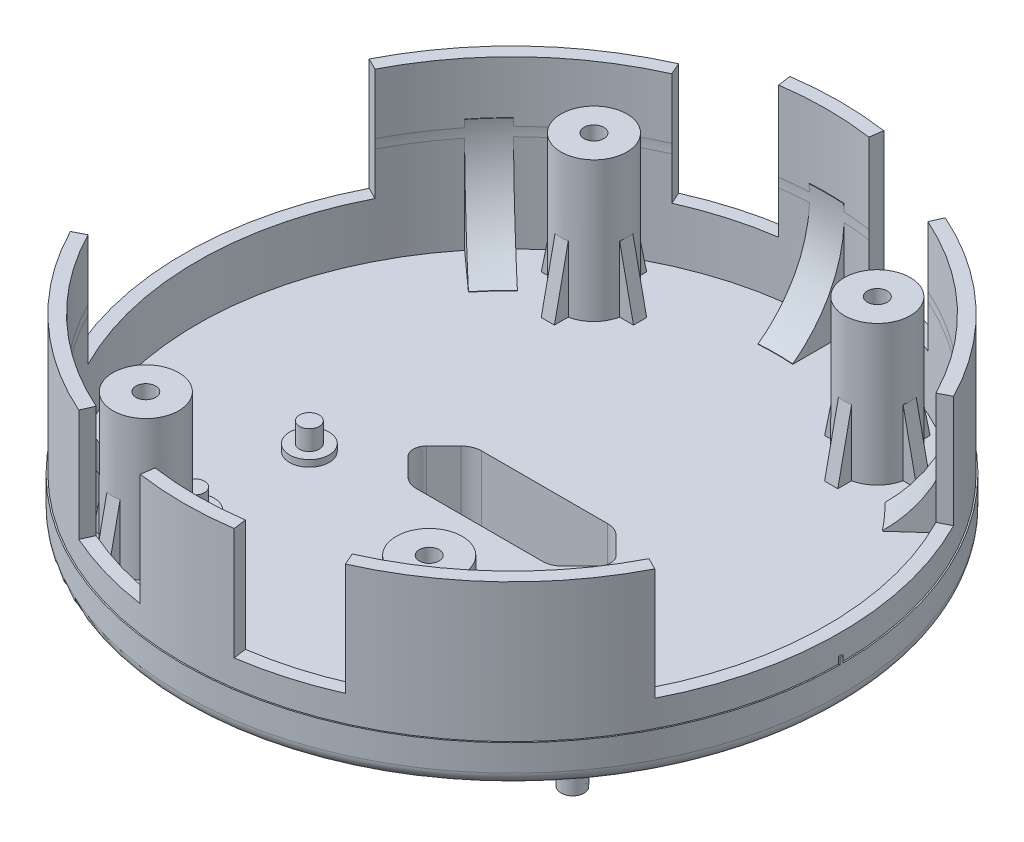
SolidWorks part; units mm, degrees
ref_plane "Front Plane" through (0, 0, 0) normal (0, 0, 1) x (1, 0, 0)
ref_plane "Top Plane" through (0, 0, 0) normal (0, 1, 0) x (1, 0, 0)
ref_plane "Right Plane" through (0, 0, 0) normal (1, 0, 0) x (0, 0, -1)
sketch "Эскиз1" plane through (0, 0, 0) normal (0, 1, 0) x (1, 0, 0)
  circle A0 centre (0, 0) radius 50
  dimension "D1" = 100
extrude "Бобышка-Вытянуть1" add sketch "Эскиз1" along normal blind 6
shell "Оболочка1" thickness 2 removed face at (0, 6, 50)
sketch "Эскиз3" plane through (0, 2, 0) normal (0, 1, 0) x (1, 0, 0)
  circle A0 centre (0, 0) radius 48 construction
  circle A1 centre (0, 0) radius 48
extrude "Бобышка-Вытянуть2" add sketch "Эскиз3" along normal blind 2
fillet "Скругление1" radius 2 1 edges at (0, 0, 50)
sketch "Эскиз4" plane through (0, 4, 0) normal (0, 1, 0) x (1, 0, 0)
  circle A2 centre (0, 0) radius 47.8
  circle A3 centre (0, 0) radius 49.8
  dimension "D1" = 99.6
  dimension "D2" = 95.6
extrude "Бобышка-Вытянуть3" add sketch "Эскиз4" along normal blind 23
sketch "Эскиз8" plane through (0, 0, 0) normal (0, -1, 0) x (1, 0, 0)
  line L0 (-17.136, 1.486) -> (-13.1647, 5.4574)
  line L1 (-9.5574, 6.9516) -> (9.5574, 6.9516)
  line L2 (13.1647, 5.4574) -> (17.136, 1.486)
  line L3 (17.136, -1.486) -> (13.1647, -5.4574)
  line L4 (9.5574, -6.9516) -> (-9.5574, -6.9516)
  line L5 (-13.1647, -5.4574) -> (-17.136, -1.486)
  line L6 (0, 6.9516) -> (0, -6.9516) construction
  line L7 (-15.65, 0) -> (15.65, 0) construction
  arc A0 (-9.5574, 6.9516) -> (-13.1647, 5.4574) centre (-9.5574, 1.85) ccw
  arc A1 (13.1647, 5.4574) -> (9.5574, 6.9516) centre (9.5574, 1.85) ccw
  arc A2 (17.136, -1.486) -> (17.136, 1.486) centre (15.65, 0) ccw
  arc A3 (9.5574, -6.9516) -> (13.1647, -5.4574) centre (9.5574, -1.85) ccw
  arc A4 (-13.1647, -5.4574) -> (-9.5574, -6.9516) centre (-9.5574, -1.85) ccw
  arc A5 (-17.136, 1.486) -> (-17.136, -1.486) centre (-15.65, 0) ccw
  circle A6 centre (0, 0) radius 48 construction
  dimension "D1" = 5.1016
  dimension "D2" = 2.1016
  dimension "D3" = 9.5574
  dimension "D4" = 15.65
  dimension "D5" = 9.5574
  dimension "D6" = 1.486
extrude "Бобышка-Вытянуть4" add sketch "Эскиз8" along normal blind 20
sketch "Эскиз9" plane through (0, 4, 0) normal (0, 1, 0) x (1, 0, 0)
  line L0 (-14.3803, 1.4134) -> (-11.7505, 4.0431)
  line L1 (-11.7505, -4.0431) -> (-14.3803, -1.4134)
  line L2 (9.5574, -4.9516) -> (-9.5574, -4.9516)
  line L3 (14.3803, -1.4134) -> (11.7505, -4.0431)
  line L4 (11.7505, 4.0431) -> (14.3803, 1.4134)
  line L5 (-9.5574, 4.9516) -> (9.5574, 4.9516)
  line L6 (0, 4.9516) -> (0, -4.9516) construction
  line L7 (-10.9611, 0) -> (10.9611, 0) construction
  arc A0 (-11.7505, -4.0431) -> (-9.5574, -4.9516) centre (-9.5574, -1.85) ccw
  arc A1 (9.5574, -4.9516) -> (11.7505, -4.0431) centre (9.5574, -1.85) ccw
  arc A2 (11.7505, 4.0431) -> (9.5574, 4.9516) centre (9.5574, 1.85) ccw
  arc A3 (-9.5574, 4.9516) -> (-11.7505, 4.0431) centre (-9.5574, 1.85) ccw
  circle A4 centre (0, 0) radius 49.8 construction
  ellipse E0 centre (-12.9635, 0) end of major axis (-10.9611, 0) minor radius 2 (-14.3803, 1.4134) -> (-14.3803, -1.4134) ccw
  ellipse E1 centre (12.9635, 0) end of major axis (10.9611, 0) minor radius 2 (14.3803, -1.4134) -> (14.3803, 1.4134) ccw
  dimension "D1" = 3.1016
  dimension "D2" = 9.5574
  dimension "D3" = 10.9611
  dimension "D4" = 12.9635
  dimension "D5" = 14.3803
  dimension "D6" = 9.5574
  dimension "D7" = 10.9611
  dimension "D8" = 1.85
  dimension "D9" = 1.85
extrude "Вырез-Вытянуть3" cut sketch "Эскиз9" against normal blind 22.5
sketch "Эскиз10" plane through (0, -18.5, 0) normal (0, 1, 0) x (1, 0, 0)
  line L0 (0, 0) -> (9.4, 0) construction
  line L1 (0, 0) -> (-9.4, 0) construction
  circle A0 centre (-9.4, 0) radius 3.5
  circle A1 centre (9.4, 0) radius 3.5
  dimension "D1" = 7
  dimension "D2" = 4.9803
extrude "Бобышка-Вытянуть5" add sketch "Эскиз10" along normal blind 6
sketch "Эскиз15" plane through (0, 4, 0) normal (0, 1, 0) x (1, 0, 0)
  circle A0 centre (0, 0) radius 50
  circle A1 centre (0, 0) radius 48
  dimension "D1" = 96
  dimension "D2" = 100
extrude "Бобышка-Вытянуть9" add sketch "Эскиз15" along normal blind 2
sketch "Эскиз16" plane through (0, 4, 0) normal (0, 1, 0) x (1, 0, 0)
  line L0 (-37.2524, 30.063) -> (-31.4039, 24.7971)
  line L1 (0, 47.8) -> (2.6705, 47.8) construction
  line L2 (0, 47.8) -> (-2.5855, 47.8) construction
  line L14 (-2.5855, 47.8) -> (-2.5855, 39.9302)
  line L15 (-33.7354, 33.969) -> (-27.8829, 28.6993)
  line L24 (0, 47.8) -> (2.6705, 47.8) construction
  line L25 (2.6705, 47.8) -> (2.6705, 39.9246)
  line L33 (0, 47.8) -> (-2.5855, 47.8) construction
  line L34 (0, 0) -> (0, 14.9931) construction
  line L37 (0, 0) -> (22.7819, 0) construction
  line L38 (0, -47.8) -> (-2.5855, -47.8) construction
  line L41 (33.7354, 33.969) -> (27.8829, 28.6993)
  line L42 (37.2524, 30.063) -> (31.4039, 24.7971)
  line L43 (0, -47.8) -> (2.6705, -47.8) construction
  line L44 (0, -47.8) -> (-2.5855, -47.8) construction
  line L45 (0, -47.8) -> (2.6705, -47.8) construction
  line L46 (37.2524, -30.063) -> (31.4039, -24.7971)
  line L47 (33.7354, -33.969) -> (27.8829, -28.6993)
  line L48 (2.6705, -47.8) -> (2.6705, -39.9246)
  line L49 (-33.7354, -33.969) -> (-27.8829, -28.6993)
  line L50 (-2.5855, -47.8) -> (-2.5855, -39.9302)
  line L51 (-37.2524, -30.063) -> (-31.4039, -24.7971)
  circle A18 centre (0, 0) radius 47.8 construction
  arc A19 (-33.68, 33.919) -> (-37.2004, 30.0162) centre (0, 0) ccw
  arc A20 (-27.8829, 28.6993) -> (-31.4039, 24.7971) centre (0, 0) ccw
  arc A21 (2.6705, 47.7253) -> (-2.5855, 47.73) centre (0, 0) ccw
  arc A22 (2.6705, 39.9246) -> (-2.5855, 39.9302) centre (0, 0) ccw
  arc A23 (33.68, -33.919) -> (37.2004, -30.0162) centre (0, 0) ccw
  arc A24 (27.8829, -28.6993) -> (31.4039, -24.7971) centre (0, 0) ccw
  arc A25 (2.6705, -39.9246) -> (-2.5855, -39.9302) centre (0, 0) cw
  arc A26 (2.6705, -47.7253) -> (-2.5855, -47.73) centre (0, 0) cw
  arc A27 (-27.8829, -28.6993) -> (-31.4039, -24.7971) centre (0, 0) cw
  arc A28 (-33.68, -33.919) -> (-37.2004, -30.0162) centre (0, 0) cw
  arc A29 (27.8829, 28.6993) -> (31.4039, 24.7971) centre (0, 0) cw
  arc A30 (33.68, 33.919) -> (37.2004, 30.0162) centre (0, 0) cw
extrude "Бобышка-Вытянуть10" add sketch "Эскиз16" along normal blind 15
sketch "Эскиз27" plane through (0, 6, 0) normal (0, 1, 0) x (1, 0, 0)
  line L0 (0, 0) -> (-65.748, 0) construction
  line L1 (0, 0) -> (0, 13.4164) construction
  line L14 (49.9994, -0.2541) -> (49.7994, -0.2541)
  line L17 (49.9994, 0.2541) -> (49.7994, 0.2541)
  line L18 (-49.9994, 0.2541) -> (-49.7994, 0.2541)
  line L19 (-49.9994, -0.2541) -> (-49.7994, -0.2541)
  arc A0 (-49.9994, 0.2541) -> (-49.9994, -0.2541) centre (0, 0) ccw
  arc A2 (-49.7994, 0.2541) -> (-49.7994, -0.2541) centre (0, 0) ccw
  arc A13 (49.7994, 0.2541) -> (49.7994, -0.2541) centre (0, 0) cw
  arc A14 (49.9994, 0.2541) -> (49.9994, -0.2541) centre (0, 0) cw
extrude "Бобышка-Вытянуть14" add sketch "Эскиз27" along normal blind 1
sketch "Эскиз28" plane through (0, 4, 0) normal (0, 1, 0) x (1, 0, 0)
  line L0 (-37.2004, 30.0162) -> (-31.4039, 24.7971) construction
  line L2 (-37.2004, 30.0162) -> (-31.4039, 24.7971)
  line L5 (-33.68, 33.919) -> (-27.8829, 28.6993) construction
  line L7 (-33.68, 33.919) -> (-27.8829, 28.6993)
  line L9 (-2.5855, 47.73) -> (-2.5855, 39.9302) construction
  line L11 (-2.5855, 47.73) -> (-2.5855, 39.9302)
  line L14 (2.6705, 47.7253) -> (2.6705, 39.9246) construction
  line L16 (2.6705, 47.7253) -> (2.6705, 39.9246)
  line L19 (33.68, 33.919) -> (27.8829, 28.6993) construction
  line L21 (33.68, 33.919) -> (27.8829, 28.6993)
  line L28 (37.2004, 30.0162) -> (31.4039, 24.7971) construction
  line L30 (37.2004, 30.0162) -> (31.4039, 24.7971)
  line L38 (37.2004, -30.0162) -> (31.4039, -24.7971) construction
  line L39 (37.2004, -30.0162) -> (31.4039, -24.7971)
  line L40 (33.68, -33.919) -> (27.8829, -28.6993) construction
  line L41 (33.68, -33.919) -> (27.8829, -28.6993)
  line L42 (2.6705, -47.7253) -> (2.6705, -39.9246) construction
  line L43 (2.6705, -47.7253) -> (2.6705, -39.9246)
  line L44 (-2.5855, -47.73) -> (-2.5855, -39.9302) construction
  line L45 (-2.5855, -47.73) -> (-2.5855, -39.9302)
  line L46 (-33.68, -33.919) -> (-27.8829, -28.6993) construction
  line L47 (-33.68, -33.919) -> (-27.8829, -28.6993)
  line L48 (-37.2004, -30.0162) -> (-31.4039, -24.7971) construction
  line L49 (-37.2004, -30.0162) -> (-31.4039, -24.7971)
  arc A0 (-37.2004, 30.0162) -> (-37.2004, -30.0162) centre (0, 0) ccw construction
  arc A2 (-37.2004, 30.0162) -> (-37.2004, -30.0162) centre (0, 0) ccw
  arc A4 (-27.8829, 28.6993) -> (-31.4039, 24.7971) centre (0, 0) ccw construction
  arc A6 (-27.8829, 28.6993) -> (-31.4039, 24.7971) centre (0, 0) ccw
  arc A8 (-2.5855, 47.73) -> (-33.68, 33.919) centre (0, 0) ccw construction
  arc A10 (-2.5855, 47.73) -> (-33.68, 33.919) centre (0, 0) ccw
  arc A14 (2.6705, 39.9246) -> (-2.5855, 39.9302) centre (0, 0) ccw construction
  arc A16 (2.6705, 39.9246) -> (-2.5855, 39.9302) centre (0, 0) ccw
  arc A17 (33.68, 33.919) -> (2.6705, 47.7253) centre (0, 0) ccw construction
  arc A18 (33.68, 33.919) -> (2.6705, 47.7253) centre (0, 0) ccw
  arc A19 (31.4039, 24.7971) -> (27.8829, 28.6993) centre (0, 0) ccw construction
  arc A20 (31.4039, 24.7971) -> (27.8829, 28.6993) centre (0, 0) ccw
  arc A21 (37.2004, -30.0162) -> (37.2004, 30.0162) centre (0, 0) ccw construction
  arc A22 (37.2004, -30.0162) -> (37.2004, 30.0162) centre (0, 0) ccw
  arc A23 (27.8829, -28.6993) -> (31.4039, -24.7971) centre (0, 0) ccw construction
  arc A24 (27.8829, -28.6993) -> (31.4039, -24.7971) centre (0, 0) ccw
  arc A25 (2.6705, -47.7253) -> (33.68, -33.919) centre (0, 0) ccw construction
  arc A26 (2.6705, -47.7253) -> (33.68, -33.919) centre (0, 0) ccw
  arc A27 (-2.5855, -39.9302) -> (2.6705, -39.9246) centre (0, 0) ccw construction
  arc A28 (-2.5855, -39.9302) -> (2.6705, -39.9246) centre (0, 0) ccw
  arc A29 (-33.68, -33.919) -> (-2.5855, -47.73) centre (0, 0) ccw construction
  arc A30 (-33.68, -33.919) -> (-2.5855, -47.73) centre (0, 0) ccw
  arc A31 (-31.4039, -24.7971) -> (-27.8829, -28.6993) centre (0, 0) ccw construction
  arc A32 (-31.4039, -24.7971) -> (-27.8829, -28.6993) centre (0, 0) ccw
ref_plane "Плоскость2" through (0, 0, 0) normal (0, 0, 1) x (1, 0, 0)
sketch "Эскиз29" plane through (0, 0, 0) normal (0, 0, 1) x (1, 0, 0)
  line L1 (7.5729, -23.4603) -> (7.4167, -30.4586)
  line L10 (9.4089, -19.6) -> (9.3224, -23.4991)
  line L11 (7.4589, -19.6) -> (9.4089, -19.6)
  line L12 (7.4589, -19.6) -> (7.3729, -23.4559)
  line L13 (0, -20) -> (0, -16.8479) construction
  line L14 (9.5574, -20) -> (-9.5574, -20) construction
  line L15 (7.3729, -23.4559) -> (7.5729, -23.4603)
  line L16 (7.4167, -30.4586) -> (9.1672, -30.4972)
  line L17 (9.3224, -23.4991) -> (9.2359, -27.3983)
  line L18 (9.2359, -27.3983) -> (9.1672, -30.4972)
revolve "Повернуть4" add sketch "Эскиз29" angle 360 about L10
sketch "Эскиз30" plane through (0, 0, 0) normal (0, 0, 1) x (1, 0, 0)
  line L4 (0, -20) -> (0, -16.0591) construction
  line L5 (9.5574, -20) -> (-9.5574, -20) construction
  line L10 (-9.4076, -19.6) -> (-9.3216, -23.4559)
  line L11 (-9.4076, -19.6) -> (-11.3576, -19.6)
  line L12 (-11.3576, -19.6) -> (-11.2711, -23.4991)
  line L14 (-11.0712, -23.4949) -> (-10.9159, -30.4932)
  line L15 (-11.3576, -19.6) -> (-11.3576, -20) construction
  line L16 (-11.2711, -23.4991) -> (-11.0712, -23.4949)
  line L17 (-10.9159, -30.4932) -> (-9.1663, -30.4566)
  line L18 (-9.3216, -23.4559) -> (-9.2351, -27.3551)
  line L19 (-9.2351, -27.3551) -> (-9.1663, -30.4566)
revolve "Повернуть5" add sketch "Эскиз30" angle 360 about L10
sketch "Эскиз32" plane through (0, 0, 0) normal (0, 0, 1) x (1, 0, 0)
  line L1 (7.9675, -30.4708) -> (8.2159, -19.2736)
  line L2 (8.2159, -19.2736) -> (8.3158, -19.2758)
  line L3 (9.1672, -30.4972) -> (7.9675, -30.4708)
  line L4 (7.4167, -30.4586) -> (10.9176, -30.5362) construction
  line L6 (8.4933, -11.2777) -> (8.3158, -19.2758)
  line L9 (8.4933, -11.2777) -> (9.593, -11.3019)
  line L10 (9.593, -11.3019) -> (9.1672, -30.4972)
revolve "Вырез-Повернуть2" cut sketch "Эскиз32" angle 360 about L10
sketch "Эскиз33" plane through (0, 0, 0) normal (0, 0, 1) x (1, 0, 0)
  line L8 (-9.5913, -11.2615) -> (-9.1654, -30.4568)
  line L11 (-8.4915, -11.2373) -> (-9.5913, -11.2615)
  line L12 (-8.4915, -11.2373) -> (-8.3141, -19.2353)
  line L13 (-9.1654, -30.4568) -> (-7.9657, -30.4304)
  line L14 (-8.2141, -19.2331) -> (-8.3141, -19.2353)
  line L15 (-7.9657, -30.4304) -> (-8.2141, -19.2331)
revolve "Вырез-Повернуть3" cut sketch "Эскиз33" angle 360 about L8
chamfer "Фаска1" distance 0.2 angle 45 2 edges at (8.3158, -19.2758, 0) (-10.5136, -19.2841, 0) first distance on face at (10.6667, -12.5, 0) first distance on face at (-10.6641, -12.5, 0)
extrude "Вырез-Вытянуть11" cut sketch "Эскиз28" against normal blind 2.2538
sketch "Эскиз34" plane through (0, 27, 0) normal (0, 1, 0) x (1, 0, 0)
  line L1 (-6.8438, 47.3075) -> (-7.1302, 49.2869)
  line L2 (6.8438, 47.3075) -> (7.1302, 49.2869)
  line L7 (6.8438, -47.3075) -> (7.1302, -49.2869)
  line L8 (-6.8438, -47.3075) -> (-7.1302, -49.2869)
  line L20 (-0.0643, -46.931) -> (-0.0643, -36.9011) construction
  line L23 (-19.4216, -43.6765) -> (-20.2342, -45.504)
  line L24 (19.4216, -43.6765) -> (20.2342, -45.504)
  line L25 (19.4216, 43.6765) -> (20.2342, 45.504)
  line L26 (-19.4216, 43.6765) -> (-20.2342, 45.504)
  line L27 (-42.5581, 21.7634) -> (-44.3388, 22.674)
  line L28 (-42.5581, -21.7634) -> (-44.3388, -22.674)
  line L29 (42.5581, -21.7634) -> (44.3388, -22.674)
  line L30 (42.5581, 21.7634) -> (44.3388, 22.674)
  circle A44 centre (0, 0) radius 47.8 construction
  arc A45 (-6.8438, 47.3075) -> (-19.4216, 43.6765) centre (0, 0) ccw
  circle A46 centre (0, 0) radius 49.8 construction
  arc A47 (-7.1302, 49.2869) -> (-20.2342, 45.504) centre (0, 0) ccw
  arc A48 (-44.3388, 22.674) -> (-44.3388, -22.674) centre (0, 0) ccw
  arc A49 (-42.5581, 21.7634) -> (-42.5581, -21.7634) centre (0, 0) ccw
  arc A50 (20.2342, 45.504) -> (7.1302, 49.2869) centre (0, 0) ccw
  arc A51 (19.4216, 43.6765) -> (6.8438, 47.3075) centre (0, 0) ccw
  arc A52 (42.5581, -21.7634) -> (42.5581, 21.7634) centre (0, 0) ccw
  arc A53 (44.3388, -22.674) -> (44.3388, 22.674) centre (0, 0) ccw
  arc A54 (6.8438, -47.3075) -> (19.4216, -43.6765) centre (0, 0) ccw
  arc A55 (7.1302, -49.2869) -> (20.2342, -45.504) centre (0, 0) ccw
  arc A56 (-19.4216, -43.6765) -> (-6.8438, -47.3075) centre (0, 0) ccw
  arc A57 (-20.2342, -45.504) -> (-7.1302, -49.2869) centre (0, 0) ccw
extrude "Вырез-Вытянуть12" cut sketch "Эскиз34" against normal blind 17
sketch "Эскиз36" plane through (0, 1.7462, 0) normal (0, 1, 0) x (1, 0, 0)
  circle A0 centre (-22.6, -8.1516) radius 1.5
  circle A1 centre (22.6, -25.5516) radius 1.5
  circle A2 centre (22.6, -8.1516) radius 1.5
  circle A3 centre (-22.6, -25.5516) radius 1.5
extrude "Бобышка-Вытянуть15" add sketch "Эскиз36" along normal blind 4
sketch "Эскиз44" plane through (0, 1.7462, 0) normal (0, 1, 0) x (1, 0, 0)
  circle A0 centre (-22.6, -8.1516) radius 3
  circle A1 centre (22.6, -8.1516) radius 3
  circle A2 centre (-22.6, -25.5516) radius 3
  circle A3 centre (22.6, -25.5516) radius 3
extrude "Бобышка-Вытянуть17" add sketch "Эскиз44" along normal blind 1
sketch "Эскиз45" plane through (0, 0, 0) normal (1, 0, 0) x (0, 0, -1)
  line L0 (-47.7253, 19) -> (-39.9246, 19) construction
  line L1 (-47.7253, 19) -> (-39.9246, 19)
  line L2 (-39.9246, 19) -> (-39.9246, 1.7462) construction
  line L3 (-39.9246, 19) -> (-39.9246, 1.7462)
  line L4 (0, 0) -> (0, 15.2612) construction
  arc A0 (-47.7253, 19) -> (-39.9246, 1.7462) centre (-28.767, 17.1811) ccw
revolve "Вырез-Повернуть4" cut sketch "Эскиз45" angle 360 about L4
sketch "Эскиз47" plane through (0, 1.7462, 0) normal (0, 1, 0) x (1, 0, 0)
  line L0 (-0.0643, -46.931) -> (-0.0643, -36.9011) construction
  line L1 (0, 0) -> (7.0344, 0) construction
  line L2 (0, 0) -> (0, -4.9516) construction
  circle A0 centre (21.4357, 34) radius 5
  circle A1 centre (-21.5643, 34) radius 5
  circle A2 centre (-21.5643, -34) radius 5
  circle A3 centre (21.4357, -34) radius 5
  point P13 (-21.5643, 34)
  point P14 (0, 0)
extrude "Бобышка-Вытянуть18" add sketch "Эскиз47" along normal blind 21.25
sketch "Эскиз48" plane through (0, 22.9962, 0) normal (0, 1, 0) x (1, 0, 0)
  circle A0 centre (-21.5643, 34) radius 1.5
  circle A1 centre (21.4357, 34) radius 1.5
  circle A2 centre (21.4357, -34) radius 1.5
  circle A3 centre (-21.5643, -34) radius 1.5
  point P8 (-21.5643, 34)
  point P9 (21.4357, 34)
  point P10 (21.4357, -34)
  point P11 (-21.5643, -34)
  point P12 (21.4357, 34)
  point P13 (21.4357, 34)
extrude "Вырез-Вытянуть20" cut sketch "Эскиз48" against normal up to surface (22.9962 mm away) up to face at (0, 0, 48)
sketch "Эскиз50" plane through (0, 0, 0) normal (0, -1, 0) x (1, 0, 0)
  circle A0 centre (-21.5643, 34) radius 3.1
  circle A1 centre (21.4357, 34) radius 3.1
  circle A2 centre (21.4357, -34) radius 3.1
  circle A3 centre (-21.5643, -34) radius 3.1
  point P8 (21.4357, 34)
extrude "Вырез-Вытянуть21" cut sketch "Эскиз50" against normal blind 19
sketch "Эскиз51" plane through (0, 0, 0) normal (0, -1, 0) x (1, 0, 0)
  line L0 (0, 0) -> (0, 20) construction
  line L1 (-10, 35) -> (10, 35)
  line L2 (-10, 35) -> (-10, 20)
  line L3 (-10, 20) -> (10, 20)
  line L4 (10, 35) -> (10, 20)
  line L5 (-10, 35) -> (10, 20) construction
  line L6 (-10, 20) -> (10, 35) construction
  point P0 (0, 27.5)
  dimension "D1" = 20
  dimension "D2" = 15
extrude "Вырез-Вытянуть22" cut sketch "Эскиз51" against normal blind 0.1
sketch "Эскиз58" plane through (0, 1.7462, 0) normal (0, 1, 0) x (1, 0, 0)
  line L0 (26.4357, 34) -> (26.4357, 33) construction
  line L1 (26.4357, 35) -> (28.4357, 35)
  line L2 (20.4357, 39) -> (20.4357, 41)
  line L3 (22.4357, 29) -> (22.4357, 27)
  line L4 (-26.5643, 34) -> (-26.5643, 35) construction
  line L5 (-26.5643, 33) -> (-28.5643, 33)
  line L6 (-28.5643, 33) -> (-28.5643, 35)
  line L7 (-28.5643, 35) -> (-26.4633, 35)
  line L8 (-26.5643, 33) -> (-26.4633, 33)
  line L9 (-22.5643, 39) -> (-22.5643, 41)
  line L10 (-22.5643, 41) -> (-20.5643, 41)
  line L11 (-20.5643, 41) -> (-20.5643, 38.899)
  line L12 (-22.5643, 39) -> (-22.5643, 38.899)
  line L13 (-21.5643, 39) -> (-20.5643, 39) construction
  line L14 (-16.5643, 35) -> (-14.5643, 35)
  line L15 (-14.5643, 35) -> (-14.5643, 33)
  line L16 (-14.5643, 33) -> (-16.6653, 33)
  line L17 (-16.5643, 35) -> (-16.6653, 35)
  line L18 (-16.5643, 34) -> (-16.5643, 33) construction
  line L19 (-20.5643, 29) -> (-20.5643, 27)
  line L20 (-20.5643, 27) -> (-22.5643, 27)
  line L21 (-22.5643, 27) -> (-22.5643, 29.101)
  line L22 (-20.5643, 29) -> (-20.5643, 29.101)
  line L23 (-21.5643, 29) -> (-22.5643, 29) construction
  line L24 (20.4357, 27) -> (20.4357, 29.101)
  line L25 (22.4357, 41) -> (22.4357, 38.899)
  line L26 (21.4357, 29) -> (20.4357, 29) construction
  line L27 (26.4357, 35) -> (26.3347, 35)
  line L28 (16.4357, 34) -> (16.4357, 35) construction
  line L29 (14.4357, 33) -> (14.4357, 35)
  line L30 (20.4357, 39) -> (20.4357, 38.899)
  line L31 (22.4357, 27) -> (20.4357, 27)
  line L32 (28.4357, 35) -> (28.4357, 33)
  line L33 (14.4357, 35) -> (16.5367, 35)
  line L34 (28.4357, 33) -> (26.3347, 33)
  line L35 (22.4357, 29) -> (22.4357, 29.101)
  line L36 (21.4357, 39) -> (22.4357, 39) construction
  line L37 (16.4357, 33) -> (14.4357, 33)
  line L38 (20.4357, 41) -> (22.4357, 41)
  line L39 (16.4357, 33) -> (16.5367, 33)
  line L41 (14.4357, -33) -> (16.5367, -33)
  line L42 (-26.5643, -34) -> (-26.5643, -33) construction
  line L43 (-14.5643, -33) -> (-14.5643, -35)
  line L44 (-20.5643, -39) -> (-20.5643, -41)
  line L45 (16.4357, -35) -> (16.5367, -35)
  line L47 (28.4357, -33) -> (28.4357, -35)
  line L48 (22.4357, -39) -> (22.4357, -41)
  line L49 (-20.5643, -39) -> (-20.5643, -38.899)
  line L50 (16.4357, -34) -> (16.4357, -33) construction
  line L51 (-26.5643, -35) -> (-28.5643, -35)
  line L52 (20.4357, -41) -> (20.4357, -38.899)
  line L54 (26.4357, -33) -> (28.4357, -33)
  line L55 (-28.5643, -33) -> (-26.4633, -33)
  line L57 (-16.5643, -33) -> (-16.6653, -33)
  line L58 (-16.5643, -34) -> (-16.5643, -35) construction
  line L59 (-28.5643, -35) -> (-28.5643, -33)
  line L61 (26.4357, -33) -> (26.3347, -33)
  line L62 (16.4357, -35) -> (14.4357, -35)
  line L64 (28.4357, -35) -> (26.3347, -35)
  line L66 (22.4357, -41) -> (20.4357, -41)
  line L67 (-22.5643, -41) -> (-22.5643, -38.899)
  line L68 (-21.5643, -39) -> (-22.5643, -39) construction
  line L70 (26.4357, -34) -> (26.4357, -35) construction
  line L71 (-14.5643, -35) -> (-16.6653, -35)
  line L72 (14.4357, -35) -> (14.4357, -33)
  line L73 (22.4357, -39) -> (22.4357, -38.899)
  line L75 (-16.5643, -33) -> (-14.5643, -33)
  line L76 (-26.5643, -35) -> (-26.4633, -35)
  line L78 (-20.5643, -41) -> (-22.5643, -41)
  line L79 (21.4357, -39) -> (20.4357, -39) construction
  circle A3 centre (-21.5643, 34) radius 5 construction
  arc A7 (-26.4633, 35) -> (-26.4633, 33) centre (-21.5643, 34) ccw
  arc A8 (-20.5643, 38.899) -> (-22.5643, 38.899) centre (-21.5643, 34) ccw
  arc A9 (-16.6653, 33) -> (-16.6653, 35) centre (-21.5643, 34) ccw
  arc A10 (-22.5643, 29.101) -> (-20.5643, 29.101) centre (-21.5643, 34) ccw
  arc A11 (20.4357, 29.101) -> (22.4357, 29.101) centre (21.4357, 34) ccw
  arc A12 (26.3347, 33) -> (26.3347, 35) centre (21.4357, 34) ccw
  arc A13 (16.5367, 35) -> (16.5367, 33) centre (21.4357, 34) ccw
  arc A14 (22.4357, 38.899) -> (20.4357, 38.899) centre (21.4357, 34) ccw
  arc A15 (20.4357, -38.899) -> (22.4357, -38.899) centre (21.4357, -34) ccw
  arc A16 (26.3347, -35) -> (26.3347, -33) centre (21.4357, -34) ccw
  arc A17 (16.5367, -33) -> (16.5367, -35) centre (21.4357, -34) ccw
  arc A18 (-22.5643, -38.899) -> (-20.5643, -38.899) centre (-21.5643, -34) ccw
  arc A19 (-26.4633, -33) -> (-26.4633, -35) centre (-21.5643, -34) ccw
  arc A22 (-16.6653, -35) -> (-16.6653, -33) centre (-21.5643, -34) ccw
  dimension "D1" = 4
extrude "Бобышка-Вытянуть19" add sketch "Эскиз58" along normal blind 10
sketch "Эскиз59" plane through (0, 0, -33) normal (0, 0, 1) x (1, 0, 0)
  line L0 (-28.5643, 11.7462) -> (-26.4633, 11.7462) construction
  line L1 (-28.5643, 11.7462) -> (-26.4633, 11.7462)
  line L2 (-28.5643, 11.7462) -> (-28.5643, 1.7462) construction
  line L3 (-28.5643, 11.7462) -> (-28.5643, 1.7462)
  line L4 (-16.6653, 11.7462) -> (-14.5643, 11.7462) construction
  line L5 (-16.6653, 11.7462) -> (-14.5643, 11.7462)
  line L6 (-14.5643, 11.7462) -> (-14.5643, 1.7462) construction
  line L7 (-14.5643, 11.7462) -> (-14.5643, 1.7462)
  line L8 (14.4357, 11.7462) -> (16.5367, 11.7462) construction
  line L9 (14.4357, 11.7462) -> (16.5367, 11.7462)
  line L10 (14.4357, 11.7462) -> (14.4357, 1.7462) construction
  line L11 (14.4357, 11.7462) -> (14.4357, 1.7462)
  line L12 (26.3347, 11.7462) -> (28.4357, 11.7462) construction
  line L13 (26.3347, 11.7462) -> (28.4357, 11.7462)
  line L14 (28.4357, 11.7462) -> (28.4357, 1.7462) construction
  line L15 (28.4357, 11.7462) -> (28.4357, 1.7462)
  line L16 (-26.4633, 11.7462) -> (-28.5643, 1.7462)
  line L17 (-16.6653, 11.7462) -> (-14.5643, 1.7462)
  line L18 (16.5367, 11.7462) -> (14.4357, 1.7462)
  line L19 (26.3347, 11.7462) -> (28.4357, 1.7462)
extrude "Вырез-Вытянуть23" cut sketch "Эскиз59" against normal up to surface (2 mm away) up to face at (-15.6148, 6.7462, -35)
sketch "Эскиз60" plane through (-20.5643, 0, 0) normal (1, 0, 0) x (0, 0, -1)
  line L0 (-41, 11.7462) -> (-38.899, 11.7462) construction
  line L1 (-41, 11.7462) -> (-38.899, 11.7462)
  line L2 (-41, 11.7462) -> (-41, 1.7462) construction
  line L3 (-41, 11.7462) -> (-41, 1.7462)
  line L4 (27, 11.7462) -> (29.101, 11.7462) construction
  line L5 (27, 11.7462) -> (29.101, 11.7462)
  line L6 (27, 11.7462) -> (27, 1.7462) construction
  line L7 (27, 11.7462) -> (27, 1.7462)
  line L8 (38.899, 11.7462) -> (41, 11.7462) construction
  line L9 (38.899, 11.7462) -> (41, 11.7462)
  line L10 (41, 11.7462) -> (41, 1.7462) construction
  line L11 (41, 11.7462) -> (41, 1.7462)
  line L12 (-38.899, 11.7462) -> (-41, 1.7462)
  line L13 (29.101, 11.7462) -> (27, 1.7462)
  line L14 (38.899, 11.7462) -> (41, 1.7462)
extrude "Вырез-Вытянуть25" cut sketch "Эскиз60" against normal up to surface (2 mm away) up to face at (-22.5643, 6.7462, 39.9495)
sketch "Эскиз61" plane through (0, 0, 33) normal (0, 0, -1) x (-1, 0, 0)
  line L0 (28.5643, 11.7462) -> (28.5643, 1.7462) construction
  line L1 (26.4633, 11.7462) -> (28.5643, 11.7462) construction
  line L2 (14.5643, 11.7462) -> (14.5643, 1.7462) construction
  line L3 (14.5643, 11.7462) -> (16.6653, 11.7462) construction
  line L4 (-28.4357, 11.7462) -> (-28.4357, 1.7462) construction
  line L5 (-28.4357, 11.7462) -> (-26.3347, 11.7462) construction
  line L6 (-14.4357, 11.7462) -> (-14.4357, 1.7462) construction
  line L7 (-16.5367, 11.7462) -> (-14.4357, 11.7462) construction
  line L8 (28.5643, 11.7462) -> (28.5643, 1.7462)
  line L9 (26.4633, 11.7462) -> (28.5643, 11.7462)
  line L10 (14.5643, 11.7462) -> (14.5643, 1.7462)
  line L11 (14.5643, 11.7462) -> (16.6653, 11.7462)
  line L12 (-28.4357, 11.7462) -> (-28.4357, 1.7462)
  line L13 (-28.4357, 11.7462) -> (-26.3347, 11.7462)
  line L14 (-14.4357, 11.7462) -> (-14.4357, 1.7462)
  line L15 (-16.5367, 11.7462) -> (-14.4357, 11.7462)
  line L16 (16.6653, 11.7462) -> (14.5643, 1.7462)
  line L17 (26.4633, 11.7462) -> (28.5643, 1.7462)
  line L18 (-16.5367, 11.7462) -> (-14.4357, 1.7462)
  line L19 (-26.3347, 11.7462) -> (-28.4357, 1.7462)
extrude "Вырез-Вытянуть26" cut sketch "Эскиз61" against normal up to surface (2 mm away) up to face at (15.4862, 6.7462, 35)
sketch "Эскиз62" plane through (20.4357, 0, 0) normal (-1, 0, 0) x (0, 0, 1)
  line L0 (41, 11.7462) -> (41, 1.7462) construction
  line L1 (38.899, 11.7462) -> (41, 11.7462) construction
  line L2 (-41, 11.7462) -> (-41, 1.7462) construction
  line L3 (-41, 11.7462) -> (-38.899, 11.7462) construction
  line L4 (-27, 11.7462) -> (-27, 1.7462) construction
  line L5 (-29.101, 11.7462) -> (-27, 11.7462) construction
  line L6 (41, 11.7462) -> (41, 1.7462)
  line L7 (38.899, 11.7462) -> (41, 11.7462)
  line L8 (-41, 11.7462) -> (-41, 1.7462)
  line L9 (-41, 11.7462) -> (-38.899, 11.7462)
  line L10 (-27, 11.7462) -> (-27, 1.7462)
  line L11 (-29.101, 11.7462) -> (-27, 11.7462)
  line L12 (38.899, 11.7462) -> (41, 1.7462)
  line L13 (-29.101, 11.7462) -> (-27, 1.7462)
  line L14 (-38.899, 11.7462) -> (-41, 1.7462)
extrude "Вырез-Вытянуть27" cut sketch "Эскиз62" against normal up to surface (2 mm away) up to face at (22.4357, 6.7462, -28.0505)
sketch "Эскиз64" plane through (0, 27, 0) normal (0, 1, 0) x (1, 0, 0)
  line L0 (7.1302, 49.2869) -> (6.8438, 47.3075) construction
  line L1 (-6.8438, 47.3075) -> (-7.1302, 49.2869) construction
  line L2 (7.1302, 49.2869) -> (6.8438, 47.3075)
  line L3 (-6.8438, 47.3075) -> (-7.1302, 49.2869)
  arc A0 (7.1302, 49.2869) -> (-7.1302, 49.2869) centre (0, 0) ccw construction
  arc A1 (6.8438, 47.3075) -> (-6.8438, 47.3075) centre (0, 0) ccw construction
  arc A2 (7.1302, 49.2869) -> (-7.1302, 49.2869) centre (0, 0) ccw
  arc A3 (6.8438, 47.3075) -> (-6.8438, 47.3075) centre (0, 0) ccw
extrude "Бобышка-Вытянуть21" add sketch "Эскиз64" along normal blind 3
